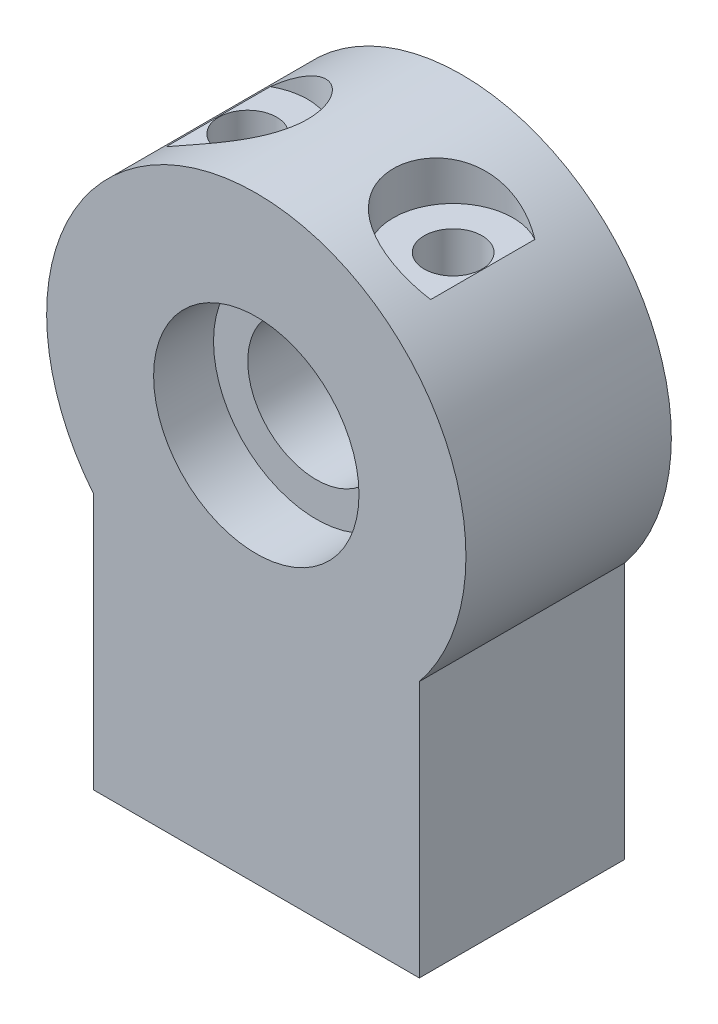
SolidWorks part; units mm, degrees
ref_plane "Front Plane" through (0, 0, 0) normal (0, 0, 1) x (1, 0, 0)
ref_plane "Top Plane" through (0, 0, 0) normal (0, 1, 0) x (1, 0, 0)
ref_plane "Right Plane" through (0, 0, 0) normal (1, 0, 0) x (0, 0, -1)
sketch "Sketch1" plane through (0, 0, 0) normal (0, 0, 1) x (1, 0, 0)
  line L0 (-19.05, -45.4) -> (19.05, -45.4)
  line L1 (19.05, -45.4) -> (19.05, -15.4)
  line L3 (-19.05, -45.4) -> (-19.05, -15.4)
  line L5 (0, -51.8676) -> (0, 51.8676) construction
  circle A0 centre (0, 0) radius 12
  arc A1 (-19.05, -15.4) -> (19.05, -15.4) centre (0, 0) cw
  point P9 (0, -45.4)
  dimension "D1" = 24
  dimension "D2" = 38.1
  dimension "D3" = 30
  dimension "D4" = 45.4
extrude "Boss-Extrude1" add sketch "Sketch1" along normal blind 7
sketch "Sketch2" plane through (0, 0, 0) normal (0, 0, 1) x (1, 0, 0)
  line L0 (-19.05, -45.4) -> (19.05, -45.4)
  line L1 (19.05, -45.4) -> (19.05, -15.4)
  line L3 (-19.05, -45.4) -> (-19.05, -15.4)
  circle A0 centre (0, 0) radius 8
  arc A1 (-19.05, -15.4) -> (19.05, -15.4) centre (0, 0) cw
  dimension "D1" = 16
  dimension "D2" = 38.1
  dimension "D3" = 30
  dimension "D4" = 45.4
extrude "Boss-Extrude2" add sketch "Sketch2" against normal blind 17
sketch "Sketch3" plane through (0, 0, 0) normal (0, 1, 0) x (1, 0, 0)
  line L0 (-12, 4) -> (12, 4) construction
  line L1 (0, -13.2) -> (0, 13.2) construction
  circle A0 centre (-12, 4) radius 3.38
  circle A1 centre (12, 4) radius 3.38
  point P4 (0, 4)
  dimension "D1" = 24
  dimension "D2" = 6.76
  dimension "D3" = 6.76
  dimension "D4" = 4
extrude "Cut-Extrude1" cut sketch "Sketch3" against normal through all both and the other way through all
sketch "Sketch4" plane through (0, 0, 0) normal (0, 1, 0) x (1, 0, 0)
  circle A0 centre (-12, 4) radius 7
  circle A1 centre (12, 4) radius 7
  dimension "D1" = 14
extrude "Cut-Extrude2" cut sketch "Sketch4" against normal blind 17 from offset 36
equation "\"bearingOuterDiameter\"= 24mm"
equation "\"bearingDepth\"= 7mm"
equation "\"holeDiameter\"= 6.76mm"
equation "\"D1@Sketch1\"=\"bearingOuterDiameter\""
equation "\"D2@Sketch1\"=25.4*1.5"
equation "\"D1@Boss-Extrude1\"=\"bearingDepth\""
equation "\"D2@Sketch3\"=\"holeDiameter\""
equation "\"D3@Sketch3\"=\"holeDiameter\""
